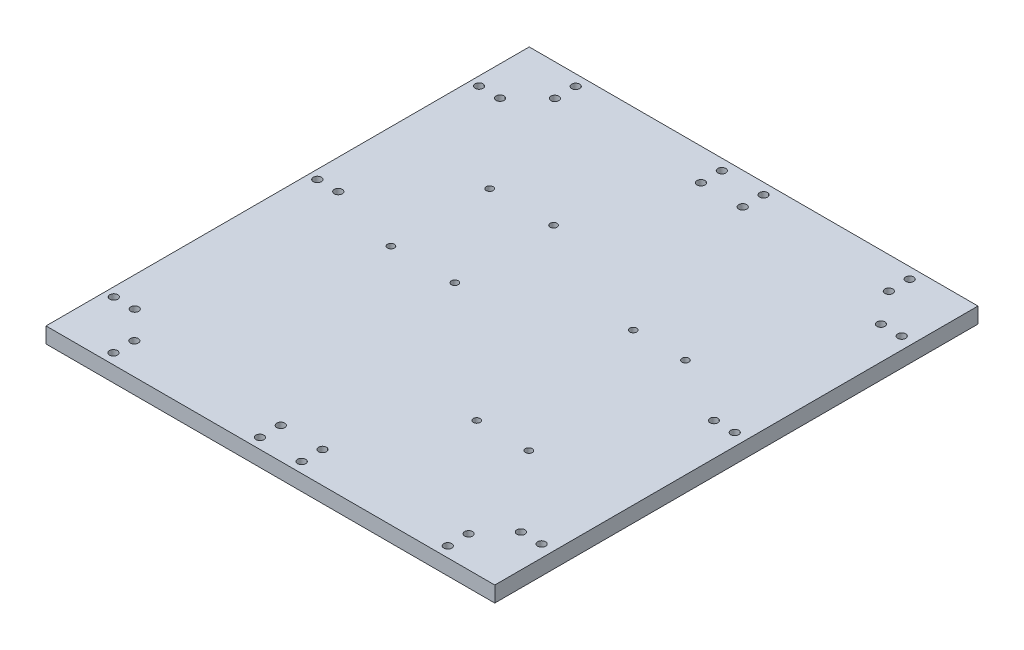
SolidWorks part; units mm, degrees
ref_plane "Front Plane" through (0, 0, 0) normal (0, 0, 1) x (1, 0, 0)
ref_plane "Top Plane" through (0, 0, 0) normal (0, 1, 0) x (1, 0, 0)
ref_plane "Right Plane" through (0, 0, 0) normal (1, 0, 0) x (0, 0, -1)
sketch "Sketch1" plane through (0, 0, 0) normal (0, 1, 0) x (1, 0, 0)
  line L1 (-215, -231.5) -> (215, -231.5)
  line L2 (-215, -231.5) -> (-215, 231.5)
  line L3 (-215, 231.5) -> (215, 231.5)
  line L4 (215, -231.5) -> (215, 231.5)
  line L5 (-215, -231.5) -> (215, 231.5) construction
  line L6 (-215, 231.5) -> (215, -231.5) construction
  point P0 (0, 0)
  dimension "D1" = 430
  dimension "D2" = 463
extrude "Boss-Extrude1" add sketch "Sketch1" along normal blind 15
sketch "Sketch6" plane through (0, 15, 0) normal (0, 1, 0) x (1, 0, 0)
  circle A0 centre (119.7933, 46.3731) radius 3.3
  circle A1 centre (69.7933, 46.3731) radius 3.3
  circle A2 centre (119.7933, -103.6269) radius 3.3
  circle A3 centre (69.7933, -103.6269) radius 3.3
sketch "Sketch7" plane through (0, 15, 0) normal (0, 1, 0) x (1, 0, 0)
  circle A0 centre (-116.3627, 94.9459) radius 3.3
  circle A1 centre (-55.3632, 95.1916) radius 3.3
  circle A2 centre (-54.9804, 0.1924) radius 3.3
  circle A3 centre (-115.98, -0.0534) radius 3.3
sketch "Sketch12" plane through (0, 0, 0) normal (0, -1, 0) x (-1, 0, 0)
  circle A0 centre (-183.5287, -175) radius 3.8
  circle A1 centre (-203.3989, 170) radius 3.8
  circle A3 centre (-183.5287, 10) radius 3.8
  circle A4 centre (-203.3989, 10) radius 3.8
  circle A5 centre (-203.3989, -175) radius 3.8
  circle A6 centre (-183.5287, 170) radius 3.8
  circle A7 centre (206.5253, -175) radius 3.8
  circle A8 centre (206.5253, 20) radius 3.8
  circle A9 centre (186.4469, 175) radius 3.8
  circle A10 centre (206.5253, 175) radius 3.8
  circle A11 centre (186.4469, -175) radius 3.8
  circle A12 centre (186.4469, 20) radius 3.8
  circle A13 centre (160.3499, -221.5206) radius 3.8
  circle A14 centre (160.3499, -201.5484) radius 3.8
  circle A15 centre (20, -221.5206) radius 3.8
  circle A16 centre (20, -201.5484) radius 3.8
  circle A17 centre (-20, -201.5484) radius 3.8
  circle A19 centre (-20, -221.5206) radius 3.8
  circle A20 centre (-160, -221.5206) radius 3.8
  circle A21 centre (-160, -201.5484) radius 3.8
  circle A22 centre (160, 201.0677) radius 3.8
  circle A23 centre (160, 221.0364) radius 3.8
  circle A24 centre (20, 201.0677) radius 3.8
  circle A25 centre (20, 221.0364) radius 3.8
  circle A26 centre (-20, 201.0677) radius 3.8
  circle A27 centre (-20, 221.0364) radius 3.8
  circle A28 centre (-160, 201.0677) radius 3.8
  circle A29 centre (-160, 221.0364) radius 3.8
  point P54 (0, 0)
extrude "Cut-Extrude3" cut sketch "Sketch12" against normal blind 50.8
extrude "Cut-Extrude4" cut sketch "Sketch6" against normal blind 50.8
extrude "Cut-Extrude5" cut sketch "Sketch7" against normal blind 50.8
